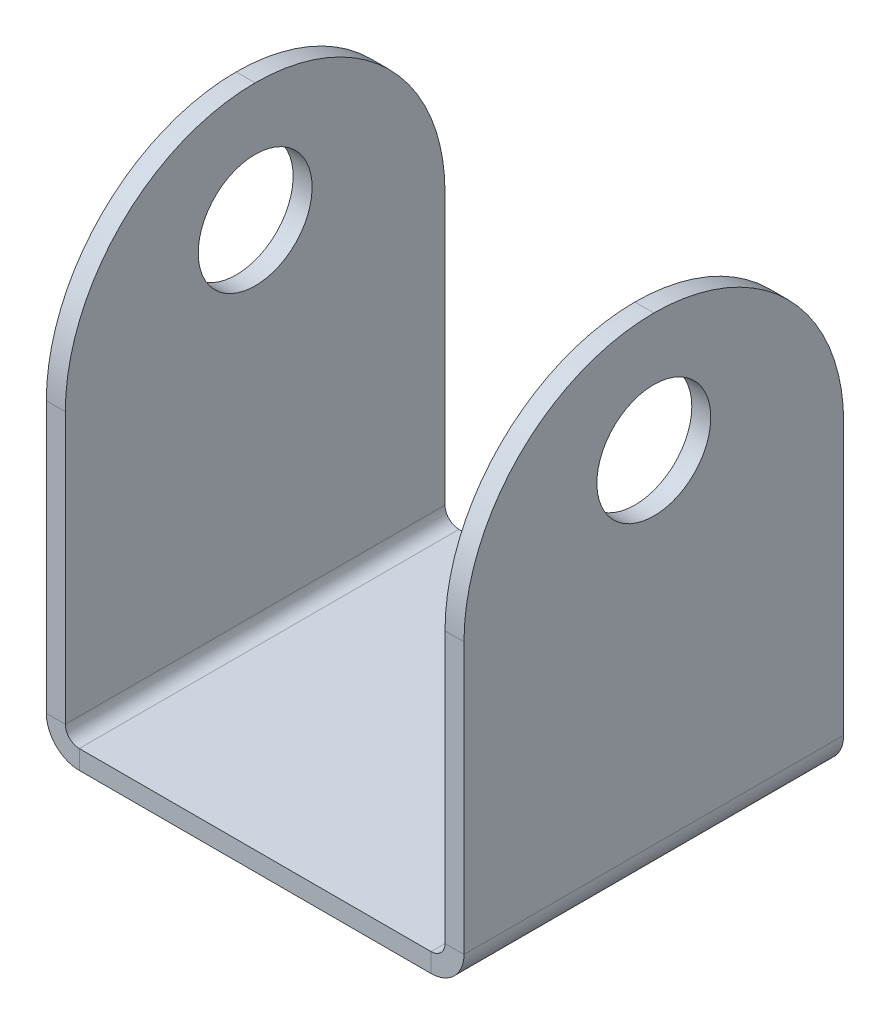
SolidWorks part; units mm, degrees
note: The reader was unsure of these and kept them because the rebuilt part matched: thickness of "Brida base1", "Brida de arista1", "Chapa metálica1", "Chapa metálica2", "Chapa metálica3", "Chapa metálica4"; flange length of "Brida de arista1".
ref_plane "Alzado" through (0, 0, 0) normal (0, 0, 1) x (1, 0, 0)
ref_plane "Planta" through (0, 0, 0) normal (0, 1, 0) x (1, 0, 0)
ref_plane "Vista lateral" through (0, 0, 0) normal (1, 0, 0) x (0, 0, -1)
sketch "Croquis1" plane through (0, 0, 0) normal (0, 1, 0) x (1, 0, 0)
  line L1 (-10, -10) -> (10, -10)
  line L2 (-10, -10) -> (-10, 10)
  line L3 (-10, 10) -> (10, 10)
  line L4 (10, -10) -> (10, 10)
  line L5 (-10, -10) -> (10, 10) construction
  line L6 (-10, 10) -> (10, -10) construction
  point P0 (0, 0)
  dimension "D1" = 20
  dimension "D2" = 20
base flange "Brida base1" sketch "Croquis1" thickness 1 reverse thickness direction no parameters "D1"=0.7366
edge flange "Brida de arista1" sketch "Croquis10" flange profiles "Croquis10", "Croquis11" flange angle 90 flange length 25 bend radius 0.7366 thickness 1 parameters "D6"=10, "D8"=1
sketch "Croquis10" plane through (10, 0, 0) normal (1, 0, 0) x (0, 0, -1)
  line L0 (-10, 0) -> (10, 0) construction
  line L1 (-10, 0) -> (10, 0)
  line L2 (-10, 0) -> (-10, 25)
  line L3 (-10, 25) -> (10, 25)
  line L4 (10, 25) -> (10, 0)
sketch "Croquis11" plane through (-10, 0, 0) normal (-1, 0, 0) x (0, 0, 1)
  line L0 (-10, 0) -> (10, 0) construction
  line L1 (-10, 0) -> (10, 0)
  line L2 (-10, 0) -> (-10, 25)
  line L3 (-10, 25) -> (10, 25)
  line L4 (10, 25) -> (10, 0)
bend "Pliegue de arista1" bend radius 0.7366 bend angle 90 parameters "D5"=1
bend "Pliegue de arista2" bend radius 0.7366 bend angle 90 parameters "D5"=2
sketch "Croquis12" plane through (11, 0, 0) normal (1, 0, 0) x (0, 0, -1)
  line L0 (10, 0.7366) -> (-10, 0.7366) construction
  circle A0 centre (0, 18.7366) radius 3
  dimension "D1" = 6
  dimension "D2" = 18
extrude "Cortar-Extruir1" cut sketch "Croquis12" against normal through all
unfold "Desdoblar1" [suppressed]
sketch "Croquis12-1" plane through (14.6775, -3.175, 0) normal (0, -1, 0) x (0, 0, -1)
  line L0 (12.5, 0.7366) -> (-12.5, 0.7366) construction
  circle A0 centre (0, 10.7366) radius 3
  dimension "D1" = 6
  dimension "D2" = 10
sketch "Croquis13" plane through (11, 0, 0) normal (1, 0, 0) x (0, 0, -1)
  line L0 (-10, 12.8683) -> (10, 12.8683) construction
  line L4 (-10, 0.7366) -> (10, 0.7366)
  line L5 (10, 0.7366) -> (10, 25)
  line L6 (10, 25) -> (-10, 25)
  line L7 (-10, 25) -> (-10, 0.7366)
  line L8 (-10, 0.7366) -> (10, 0.7366)
  line L9 (10, 0.7366) -> (10, 25)
  line L10 (10, 25) -> (-10, 25)
  line L11 (-10, 25) -> (-10, 0.7366)
  arc A0 (-10, 12.8683) -> (10, 12.8683) centre (0, 8.2857) cw
  line M9 (10, 25) -> (-10, 25)
  line M10 (-10, 25) -> (-10, 0.7366)
  dimension "D2" = 11
  dimension "D1" = 0
extrude "Cortar-Extruir2" [suppressed] cut sketch "Croquis13" against normal through all contours A0 L9 M10 M9
fillet "Redondeo1" radius 10 4 edges at (-10.5, 25, -10) (10.5, 25, -10) (10.5, 25, 10) (-10.5, 25, 10)
ref_point "Point1"
sketch "Líneas de pliegue1" [suppressed] plane through (0, 0, 0) normal (0, 1, 0) x (1, 0, 0)
sketch "Cuadro delimitador1" [suppressed] plane through (0, 0, 0) normal (0, 1, 0) x (1, 0, 0)
sheet metal parameters "Chapa metálica1" thickness 1 parameters "D1"=0.7366, "D7"=3.175
flat pattern "Chapa desplegada1"
sketch "Líneas de pliegue2" plane through (0, 0, 0) normal (0, 1, 0) x (1, 0, 0)
sketch3d "Cuadro delimitador2" [suppressed]
  line L0 (12.5, -12.5, 0) -> (12.5, 12.5, 0) construction
  line L1 (-12.5, -12.5, 0) -> (-12.5, 12.5, 0) construction
  line L2 (12.5, -12.5, 0) -> (-12.5, -12.5, 0) construction
  line L3 (12.5, 12.5, 0) -> (-12.5, 12.5, 0) construction
sheet metal parameters "Chapa metálica2" thickness 1 parameters "D1"=0.7366, "D7"=3.175
flat pattern "Chapa desplegada1"
sketch "Líneas de pliegue2" plane through (0, 0, 0) normal (0, 1, 0) x (1, 0, 0)
  line L0 (-13.5887, 12.5) -> (-13.5887, -12.5) construction
  line L1 (13.5887, -12.5) -> (13.5887, 12.5) construction
  line L2 (-13.5887, 12.5) -> (-13.5887, -12.5) construction
  line L3 (13.5887, -12.5) -> (13.5887, 12.5) construction
sketch3d "Cuadro delimitador2" [suppressed]
  line L0 (-39.6775, 12.5, 0) -> (39.6775, 12.5, 0) construction
  line L1 (-39.6775, -12.5, 0) -> (39.6775, -12.5, 0) construction
  line L2 (-39.6775, 12.5, 0) -> (-39.6775, -12.5, 0) construction
  line L3 (39.6775, 12.5, 0) -> (39.6775, -12.5, 0) construction
bend of the flat pattern "Aplanar-<Pliegue de arista1>1"
bend of the flat pattern "Aplanar-<Pliegue de arista2>1"
sheet metal parameters "Chapa metálica3" thickness 1 parameters "D1"=0.7366, "D7"=3.175
flat pattern "Chapa desplegada1"
sketch "Líneas de pliegue2" plane through (0, 0, 0) normal (0, 1, 0) x (1, 0, 0)
  line L0 (-10.2346, 10) -> (-10.2346, -10) construction
  line L1 (10.2346, -10) -> (10.2346, 10) construction
  line L2 (-10.2346, 10) -> (-10.2346, -10) construction
  line L3 (10.2346, -10) -> (10.2346, 10) construction
sketch3d "Cuadro delimitador2" [suppressed]
  line L0 (35.4692, 10, 0) -> (-35.4692, 10, 0) construction
  line L1 (35.4692, -10, 0) -> (-35.4692, -10, 0) construction
  line L2 (35.4692, 10, 0) -> (35.4692, -10, 0) construction
  line L3 (-35.4692, 10, 0) -> (-35.4692, -10, 0) construction
bend of the flat pattern "Aplanar-<Pliegue de arista1>1"
bend of the flat pattern "Aplanar-<Pliegue de arista2>1"
sheet metal parameters "Chapa metálica4" thickness 1 parameters "D1"=0.7366, "D7"=3.175
flat pattern "Chapa desplegada1"
sketch "Líneas de pliegue2" plane through (0, 0, 0) normal (0, 1, 0) x (1, 0, 0)
  line L0 (-10.2346, 10) -> (-10.2346, -10) construction
  line L1 (10.2346, -10) -> (10.2346, 10) construction
  line L2 (-10.2346, 10) -> (-10.2346, -10) construction
  line L3 (10.2346, -10) -> (10.2346, 10) construction
sketch3d "Cuadro delimitador2" [suppressed]
  line L0 (29.3388, 10, 0) -> (-29.3388, 10, 0) construction
  line L1 (29.3388, -10, 0) -> (-29.3388, -10, 0) construction
  line L2 (29.3388, 10, 0) -> (29.3388, -10, 0) construction
  line L3 (-29.3388, 10, 0) -> (-29.3388, -10, 0) construction
bend of the flat pattern "Aplanar-<Pliegue de arista1>1"
bend of the flat pattern "Aplanar-<Pliegue de arista2>1"
